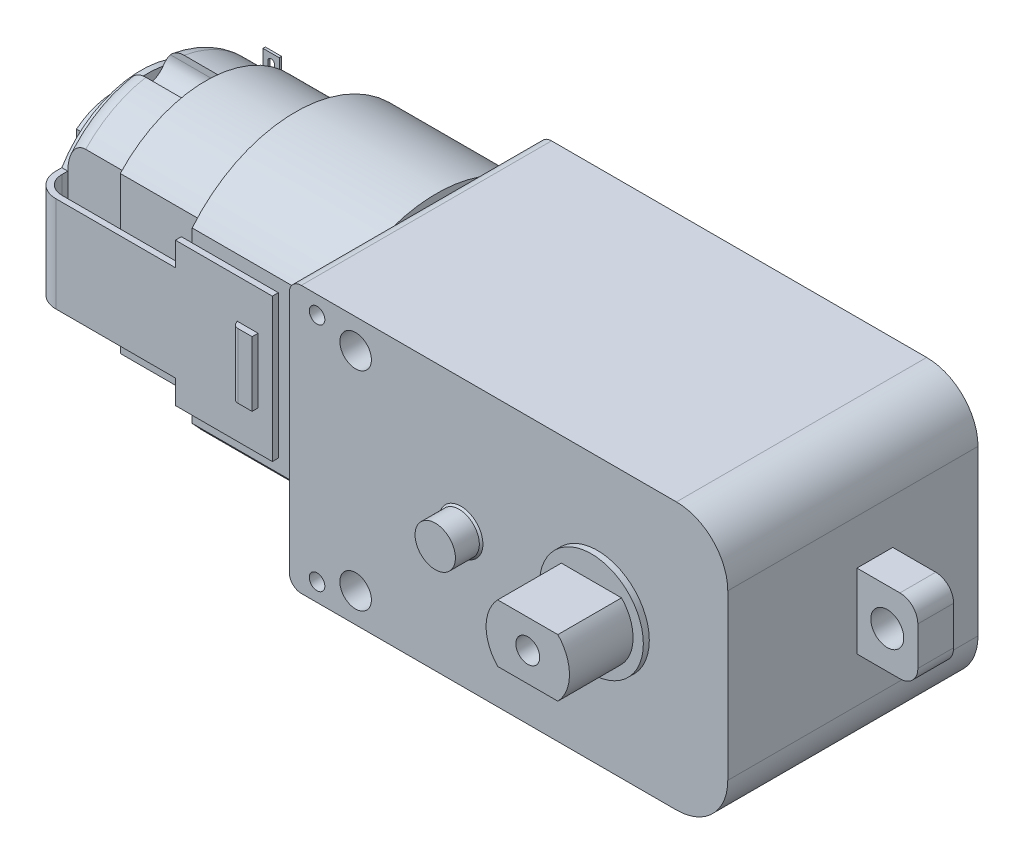
SolidWorks part; units mm, degrees
ref_plane "Plan de face" through (0, 0, 0) normal (0, 0, 1) x (1, 0, 0)
ref_plane "Plan de dessus" through (0, 0, 0) normal (0, 1, 0) x (1, 0, 0)
ref_plane "Plan de droite" through (0, 0, 0) normal (1, 0, 0) x (0, 0, -1)
sketch "Esquisse1" plane through (0, 0, 0) normal (0, 0, 1) x (1, 0, 0)
  line L0 (-45.7244, 0) -> (18.8168, 0) construction
  line L1 (0, 14.8065) -> (0, -12.8323) construction
  line L2 (-29.1715, 8.71) -> (-11.3285, 8.71) construction
  line L3 (-24.8, 11.175) -> (6.62, 11.175)
  line L4 (-25.8, 10.175) -> (-25.8, -10.175)
  line L5 (-24.8, -11.175) -> (6.62, -11.175)
  line L6 (10.92, 6.875) -> (10.92, -6.875)
  line L7 (-29.2098, -8.71) -> (-11.2902, -8.71) construction
  arc A0 (6.62, -11.175) -> (10.92, -6.875) centre (6.62, -6.875) ccw
  arc A1 (10.92, 6.875) -> (6.62, 11.175) centre (6.62, 6.875) ccw
  arc A2 (-25.8, -10.175) -> (-24.8, -11.175) centre (-24.8, -10.175) ccw
  arc A3 (-24.8, 11.175) -> (-25.8, 10.175) centre (-24.8, 10.175) ccw
  circle A4 centre (-20.25, 8.71) radius 1.32
  circle A5 centre (-20.25, -8.71) radius 1.32
  point P8 (-83.2342, 52.9238)
  dimension "D4" = 4.3
  dimension "D5" = 1
  dimension "D6" = 2.64
  dimension "D8" = 2.64
  dimension "D10" = 4.3
  dimension "D1" = 10.92
  dimension "D2" = 25.8
  dimension "D3" = 22.35
  dimension "D7" = 31.17
  dimension "D9" = 17.42
extrude "Boss.-Extru.1" add sketch "Esquisse1" along normal blind 12.32 and the other way blind 8.64
sketch "Esquisse2" plane through (-25.8, 0, 0) normal (-1, 0, 0) x (0, 0, 1)
  line L0 (-12.1786, 0) -> (13.3411, 0) construction
  line L1 (0, 14.5533) -> (0, -13.3967) construction
  line L2 (-8.64, 7.0874) -> (-8.64, -7.0874)
  line L4 (8.64, 7.0874) -> (8.64, -7.0874)
  line L5 (-8.64, 11.175) -> (12.32, 11.175) construction
  line L6 (-8.64, 10.175) -> (-8.64, -10.175) construction
  arc A0 (-8.64, -7.0874) -> (8.64, -7.0874) centre (0, 0) ccw
  arc A1 (8.64, 7.0874) -> (-8.64, 7.0874) centre (0, 0) ccw
extrude "Boss.-Extru.2" add sketch "Esquisse2" along normal blind 11.82
sketch "Esquisse3" plane through (-37.62, 0, 0) normal (-1, 0, 0) x (0, 0, 1)
  line L6 (-7.14, 6.5289) -> (-7.14, -6.5289)
  line L7 (7.14, -6.5289) -> (7.14, 6.5289)
  line L8 (-7.14, 6.5289) -> (-7.14, -6.5289)
  line L9 (7.14, -6.5289) -> (7.14, 6.5289)
  arc A6 (7.14, 6.5289) -> (-7.14, 6.5289) centre (0, 0) ccw
  arc A7 (-7.14, -6.5289) -> (7.14, -6.5289) centre (0, 0) ccw
  arc A8 (7.14, 6.5289) -> (-7.14, 6.5289) centre (0, 0) ccw
  arc A9 (-7.14, -6.5289) -> (7.14, -6.5289) centre (0, 0) ccw
  dimension "D1" = 1.5
extrude "Boss.-Extru.3" add sketch "Esquisse3" along normal blind 7.52
sketch "Esquisse4" plane through (-45.14, 0, 0) normal (-1, 0, 0) x (0, 0, 1)
  line L9 (6.64, -6.3317) -> (6.64, 6.3317)
  line L10 (-6.64, 6.3317) -> (-6.64, -6.3317)
  line L11 (6.64, -6.3317) -> (6.64, 6.3317)
  line L12 (-6.64, 6.3317) -> (-6.64, -6.3317)
  arc A9 (-6.64, -6.3317) -> (6.64, -6.3317) centre (0, 0) ccw
  arc A10 (6.64, 6.3317) -> (-6.64, 6.3317) centre (0, 0) ccw
  arc A11 (-6.64, -6.3317) -> (6.64, -6.3317) centre (0, 0) ccw
  arc A12 (6.64, 6.3317) -> (-6.64, 6.3317) centre (0, 0) ccw
  dimension "D1" = 0.5
extrude "Boss.-Extru.4" add sketch "Esquisse4" along normal blind 4.9
sketch "Esquisse5" plane through (0, 0, 12.32) normal (0, 0, 1) x (1, 0, 0)
  circle A0 centre (0, 0) radius 4.35
  dimension "D1" = 8.7
extrude "Boss.-Extru.5" add sketch "Esquisse5" along normal blind 0.5
sketch "Esquisse6" plane through (0, 0, 12.82) normal (0, 0, 1) x (1, 0, 0)
  line L0 (-2.5195, 2.415) -> (2.5195, 2.415)
  line L1 (-10.1811, 0) -> (9.7574, 0) construction
  line L2 (-2.5195, -2.415) -> (2.5195, -2.415)
  arc A0 (-2.5195, 2.415) -> (-2.5195, -2.415) centre (0, 0) ccw
  arc A1 (2.5195, -2.415) -> (2.5195, 2.415) centre (0, 0) ccw
  dimension "D1" = 6.98
  dimension "D2" = 4.83
extrude "Boss.-Extru.6" add sketch "Esquisse6" along normal blind 5.33
sketch "Esquisse7" plane through (0, 0, 0) normal (0, 0, 1) x (1, 0, 0)
  line L0 (-7.492, 0) -> (16.644, 0) construction
  line L1 (10.92, -6.875) -> (10.92, 6.875) construction
  line L2 (10.92, 3.115) -> (14.52, 3.115)
  line L3 (10.92, 3.115) -> (10.92, -3.115)
  line L4 (10.92, -3.115) -> (14.52, -3.115)
  line L5 (16.02, 1.615) -> (16.02, -1.615)
  circle A0 centre (13.46, 0) radius 1.38
  arc A1 (14.52, -3.115) -> (16.02, -1.615) centre (14.52, -1.615) ccw
  arc A2 (14.52, 3.115) -> (16.02, 1.615) centre (14.52, 1.615) cw
  point P15 (16.02, 3.115)
  dimension "D4" = 1.5
  dimension "D5" = 2.76
  dimension "D1" = 5.1
  dimension "D2" = 6.23
  dimension "D3" = 2.54
extrude "Boss.-Extru.7" add sketch "Esquisse7" along normal blind 1.5 and the other way blind 1.5
sketch "Esquisse8" plane through (0, 0, 12.32) normal (0, 0, 1) x (1, 0, 0)
  line L0 (-54.5371, 0) -> (22.0807, 0) construction
  line L1 (10.92, -6.875) -> (10.92, 6.875) construction
  circle A0 centre (-11.43, 0) radius 1.69
  dimension "D1" = 3.38
  dimension "D2" = 22.35
extrude "Boss.-Extru.8" add sketch "Esquisse8" along normal blind 2.15
chamfer "Chanfrein1" distance 0.15 angle 45 1 edges at (-9.74, 0, 12.32)
sketch "Esquisse9" plane through (0, 0, 18.15) normal (0, 0, 1) x (1, 0, 0)
  circle A0 centre (0, 0) radius 1
  dimension "D1" = 2
extrude "Enlèv. mat.-Extru.1" cut sketch "Esquisse9" against normal blind 3
sketch "Esquisse10" plane through (0, 0, 0) normal (0, 0, 1) x (1, 0, 0)
  line L0 (9.7138, 0) -> (-56.2429, 0) construction
  line L1 (-50.04, 1.1) -> (-54.29, 1.1)
  line L2 (-50.04, -6.3317) -> (-50.04, 6.3317) construction
  line L3 (-54.29, 1.1) -> (-54.29, 0)
  line L4 (-54.29, 0) -> (-50.04, 0)
  line L5 (-50.04, 0) -> (-50.04, 1.1)
  line L6 (10.92, -6.875) -> (10.92, 6.875) construction
  dimension "D1" = 65.21
  dimension "D2" = 1.1
revolve "Révolution1" add sketch "Esquisse10" angle 360 about L0
sketch "Esquisse11" plane through (0, 0, 12.32) normal (0, 0, 1) x (1, 0, 0)
  line L0 (21.3889, 0) -> (-63.9764, 0) construction
  line L1 (-23.48, 15.5821) -> (-23.48, -16.9128) construction
  line L2 (10.92, -6.875) -> (10.92, 6.875) construction
  circle A0 centre (-23.48, 9.67) radius 0.65
  circle A1 centre (-23.48, -9.67) radius 0.65
  dimension "D2" = 1.3
  dimension "D1" = 34.4
  dimension "D3" = 9.67
extrude "Enlèv. mat.-Extru.2" cut sketch "Esquisse11" against normal blind 7
sketch "Esquisse12" plane through (0, 0, -8.64) normal (0, 0, -1) x (-1, 0, 0)
  line L0 (-18.7378, 0) -> (58.447, 0) construction
  line L1 (23.48, 16.9834) -> (23.48, -15.1328) construction
  line L3 (-10.92, -6.875) -> (-10.92, 6.875) construction
  circle A0 centre (23.48, 9.67) radius 0.65
  circle A1 centre (23.48, -9.67) radius 0.65
  dimension "D3" = 1.3
  dimension "D4" = 9.67
  dimension "D1" = 34.4
extrude "Enlèv. mat.-Extru.4" cut sketch "Esquisse12" against normal blind 7
sketch "Esquisse13" plane through (-50.04, 0, 0) normal (-1, 0, 0) x (0, 0, 1)
  line L0 (0, -12.978) -> (0, 12.1367) construction
  line L1 (-1.6, 8.5) -> (-1.6, 10.8363)
  line L2 (-1.6, 10.8363) -> (1.6, 10.8363)
  line L3 (1.6, 10.8363) -> (1.6, 8.5)
  line L4 (-9.9158, 0) -> (10.2522, 0) construction
  line L5 (1.6, -10.8363) -> (1.6, -8.5)
  line L6 (-1.6, -10.8363) -> (1.6, -10.8363)
  line L7 (-1.6, -8.5) -> (-1.6, -10.8363)
  arc A0 (-1.6, 8.5) -> (1.6, 8.5) centre (0, 8.5) ccw
  arc A1 (-1.6, -8.5) -> (1.6, -8.5) centre (0, -8.5) cw
  dimension "D1" = 3.2
  dimension "D2" = 8.5
  dimension "D3" = 2.3363
extrude "Enlèv. mat.-Extru.5" cut sketch "Esquisse13" against normal up to surface (4.9 mm away) up to face at (-45.14, 0, 0)
fillet "Congé2" radius 1.5 4 edges at (-50.04, -8.0858, -4.336) (-50.04, -8.0858, 4.336) (-50.04, 8.0858, 4.336) (-50.04, 8.0858, -4.336)
sketch "Esquisse14" plane through (0, 0, 8.64) normal (0, 0, 1) x (1, 0, 0)
  line L0 (8.4304, 0) -> (-55.4587, 0) construction
  line L2 (-32.6, 2.7) -> (-30.6, 2.7)
  line L3 (-32.6, 2.7) -> (-32.6, -2.7)
  line L4 (-32.6, -2.7) -> (-30.6, -2.7)
  line L5 (-30.6, 2.7) -> (-30.6, -2.7)
  dimension "D1" = 2
  dimension "D2" = 30.6
  dimension "D3" = 5.4
extrude "Enlèv. mat.-Extru.6" cut sketch "Esquisse14" against normal blind 1
sketch "Esquisse15" plane through (0, 0, 0) normal (0, 1, 0) x (1, 0, 0)
  line L0 (-33.2382, -9.3636) -> (-33.6, -8.64)
  line L1 (-32.791, -9.64) -> (-31.6, -9.64)
  line L3 (-37.62, -8.64) -> (-25.8, -8.64) construction
  line L4 (-33.6, -8.64) -> (-32.35, -8.64)
  line L5 (-32.35, -8.64) -> (-32.35, -9.14)
  line L6 (-32.35, -9.14) -> (-31.6, -9.14)
  line L7 (-31.6, -9.14) -> (-31.6, -9.64)
  arc A0 (-33.2382, -9.3636) -> (-32.791, -9.64) centre (-32.791, -9.14) ccw
  point P12 (-33.1, -9.64)
  dimension "D7" = 0.5
  dimension "D1" = 33.6
  dimension "D2" = 1
  dimension "D3" = 1.5
  dimension "D4" = 0.5
  dimension "D5" = 0.75
  dimension "D6" = 0.5
extrude "Boss.-Extru.12" add sketch "Esquisse15" along normal blind 2.71 and the other way blind 2.71
mirror "Symétrie1" about plane through (0, 0, 0) normal (0, 0, 1) of "Enlèv. mat.-Extru.6", "Boss.-Extru.12"
sketch "Esquisse16" plane through (-50.04, 0, 0) normal (-1, 0, 0) x (0, 0, 1)
  line L0 (3.2, 3.9711) -> (3.2, -3.9711)
  arc A0 (3.2, 3.9711) -> (3.2, -3.9711) centre (0, 0) ccw
  circle A1 centre (0, 0) radius 1.1
  dimension "D1" = 10.2
  dimension "D3" = 2.2
  dimension "D2" = 3.2
extrude "Boss.-Extru.13" add sketch "Esquisse16" along normal blind 2.71
sketch "Esquisse17" plane through (0, 0, -6.64) normal (0, 0, -1) x (-1, 0, 0)
  line L0 (-5.4823, 0) -> (62.0828, 0) construction
  line L1 (45.14, 6.3317) -> (45.14, -6.3317) construction
  line L2 (45.64, 3.25) -> (50.04, 3.25)
  line L3 (45.64, 3.25) -> (45.64, -3.25)
  line L4 (45.64, -3.25) -> (50.04, -3.25)
  line L5 (50.04, 3.25) -> (50.04, -3.25)
  line L6 (50.04, 3.8492) -> (50.04, -3.8492) construction
  point P7 (47.84, -3.25)
  dimension "D1" = 6.5
  dimension "D2" = 0.5
extrude "Boss.-Extru.14" add sketch "Esquisse17" along normal blind 1
fillet "Congé3" radius 1.5 1 edges at (-50.04, 0, -7.64)
sketch "Esquisse18" plane through (0, 0, -7.64) normal (0, 0, -1) x (-1, 0, 0)
  line L0 (-4.5189, 0) -> (59.4219, 0) construction
  line L1 (46.4034, 7) -> (47.7668, 7)
  line L2 (46.4034, 7) -> (46.4034, -7)
  line L3 (46.4034, -7) -> (47.7668, -7)
  line L4 (47.7668, 7) -> (47.7668, -7)
  line L5 (45.14, 6.5289) -> (45.14, -6.5289) construction
  line L6 (47.0835, 6.3) -> (47.0835, 5.3) construction
  line L7 (47.0835, -6.3) -> (47.0835, -5.3) construction
  line L8 (47.3668, -6.3) -> (47.3668, -5.3)
  line L9 (46.8001, -6.3) -> (46.8001, -5.3)
  line L11 (47.3668, 6.3) -> (47.3668, 5.3)
  line L12 (46.8001, 6.3) -> (46.8001, 5.3)
  arc A0 (47.3668, 6.3) -> (46.8001, 6.3) centre (47.0835, 6.3) ccw
  arc A1 (46.8001, 5.3) -> (47.3668, 5.3) centre (47.0835, 5.3) ccw
  arc A2 (47.3668, -6.3) -> (46.8001, -6.3) centre (47.0835, -6.3) cw
  arc A3 (46.8001, -5.3) -> (47.3668, -5.3) centre (47.0835, -5.3) cw
  point P11 (47.0835, -5.8)
  point P15 (47.0835, 5.8)
  dimension "D1" = 1.3634
  dimension "D2" = 14
  dimension "D3" = 1.2634
  dimension "D4" = 0.3967
  dimension "D5" = 0.4
  dimension "D6" = 5.8
  dimension "D7" = 1
extrude "Boss.-Extru.15" add sketch "Esquisse18" against normal blind 0.2
sketch "Esquisse19" plane through (-50.04, 0, 0) normal (-1, 0, 0) x (0, 0, 1)
  line L0 (3.2, -3.9711) -> (3.2, 3.9711) construction
  line L1 (3.2, -3.9711) -> (3.2, 3.9711)
  arc A0 (3.2, 3.9711) -> (3.2, -3.9711) centre (0, 0) ccw construction
  arc A1 (3.2, 3.9711) -> (3.2, -3.9711) centre (0, 0) ccw
  circle A2 centre (0, 0) radius 7.75
  dimension "D1" = 15.5
extrude "Boss.-Extru.16" add sketch "Esquisse19" along normal blind 0.5
sketch "Esquisse20" plane through (0, 0, 0) normal (0, 1, 0) x (1, 0, 0)
  line L4 (-32.35, 8.64) -> (-50.54, 8.64)
  line L5 (-50.54, 8.64) -> (-50.54, 9.14)
  line L6 (-30.4038, 9.14) -> (-50.54, 9.14)
  line L7 (-32.35, 8.64) -> (-30.4038, 8.64)
  line L8 (-37.62, 8.64) -> (-25.8, 8.64) construction
  line L9 (-30.4038, 8.64) -> (-30.4038, 9.14)
  line L10 (-50.54, 7.75) -> (-50.54, -7.75) construction
extrude "Boss.-Extru.17" add sketch "Esquisse20" along normal blind 6 and the other way blind 6
sketch "Esquisse21" plane through (0, 0, -9.14) normal (0, 0, -1) x (-1, 0, 0)
  line L0 (-4.1946, 0) -> (60.8708, 0) construction
  line L1 (56.3261, -4) -> (56.3261, -8.6205)
  line L2 (38.5259, 4) -> (56.3261, 4)
  line L3 (38.5259, 4) -> (38.5259, 8.6205)
  line L4 (38.5259, 8.6205) -> (56.3261, 8.6205)
  line L5 (56.3261, 4) -> (56.3261, 8.6205)
  line L6 (38.5259, -8.6205) -> (56.3261, -8.6205)
  line L7 (38.5259, -4) -> (38.5259, -8.6205)
  line L8 (38.5259, -4) -> (56.3261, -4)
  dimension "D1" = 4
extrude "Enlèv. mat.-Extru.7" cut sketch "Esquisse21" against normal up to next
sketch "Esquisse22" plane through (-50.54, 0, 0) normal (-1, 0, 0) x (0, 0, 1)
  line L0 (4.4303, 0) -> (-12.9255, 0) construction
  line L1 (-9.14, 4) -> (-5.977, 4)
  line L2 (-9.14, 4) -> (-9.14, -4)
  line L3 (-9.14, -4) -> (-5.977, -4)
  line L4 (-5.977, 4) -> (-5.977, -4)
extrude "Boss.-Extru.18" add sketch "Esquisse22" against normal blind 0.5
fillet "Congé4" radius 1.5 1 edges at (-50.04, 0, -8.64)
fillet "Congé5" radius 2 1 edges at (-50.54, 0, -9.14)
mirror "Symétrie2" about plane through (0, 0, 0) normal (0, 0, 1) of "Congé5", "Congé4", "Boss.-Extru.18", "Enlèv. mat.-Extru.7", "Boss.-Extru.17"
